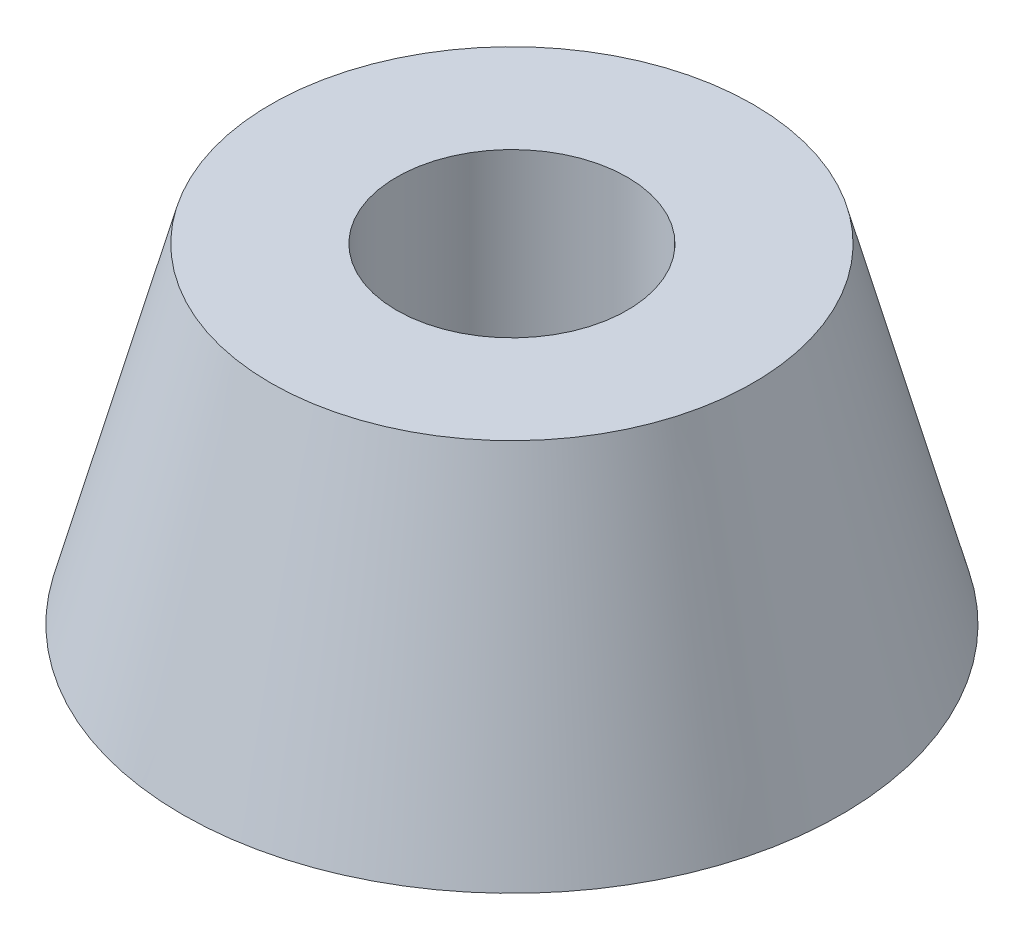
SolidWorks part; units mm, degrees
ref_plane "Plan de face" through (0, 0, 0) normal (0, 0, 1) x (1, 0, 0)
ref_plane "Plan de dessus" through (0, 0, 0) normal (0, 1, 0) x (1, 0, 0)
ref_plane "Plan de droite" through (0, 0, 0) normal (1, 0, 0) x (0, 0, -1)
sketch "Esquisse1" plane through (0, 0, 0) normal (0, 1, 0) x (1, 0, 0)
  circle A0 centre (0, 0) radius 6
  dimension "D1" = 12
extrude "Boss.-Extru.1" add sketch "Esquisse1" along normal blind 6 draft 15
sketch "Esquisse2" plane through (0, 6, 0) normal (0, 1, 0) x (1, 0, 0)
  circle A0 centre (0, 0) radius 2.1
  dimension "D1" = 4.2
extrude "Enlèv. mat.-Extru.1" cut sketch "Esquisse2" against normal up to next
